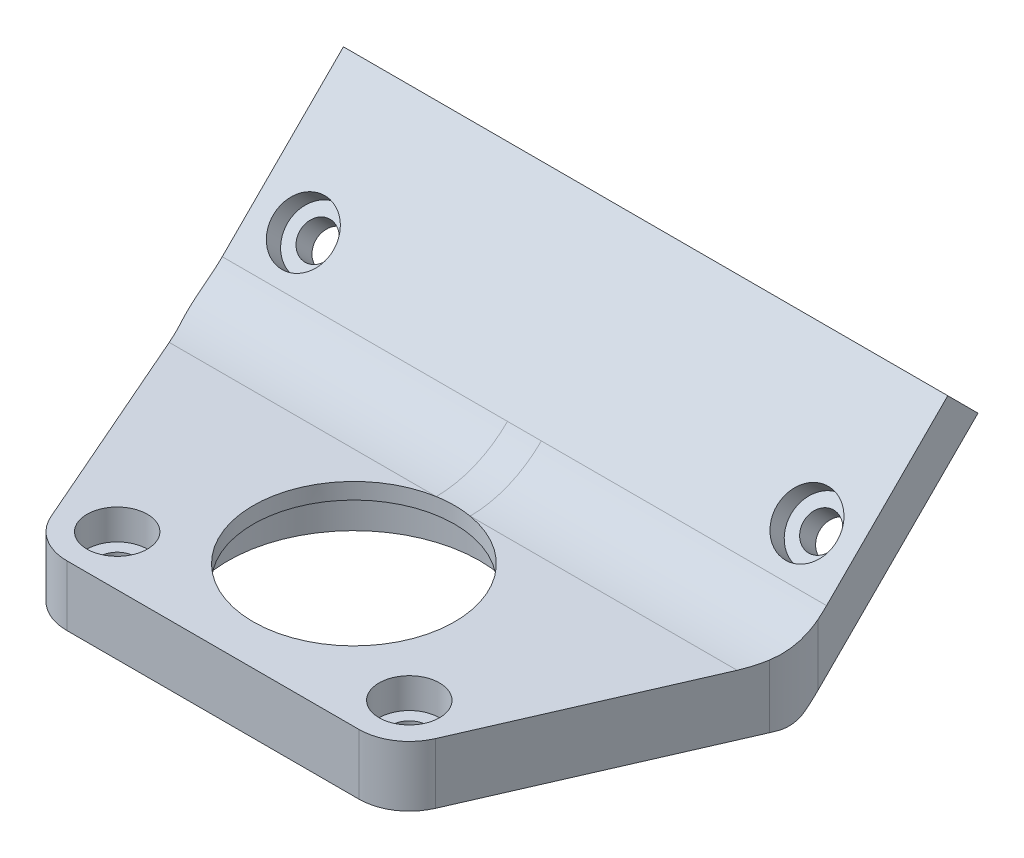
SolidWorks part; units mm, degrees
ref_plane "Alzado" through (0, 0, 0) normal (0, 0, 1) x (1, 0, 0)
ref_plane "Planta" through (0, 0, 0) normal (0, 1, 0) x (1, 0, 0)
ref_plane "Vista lateral" through (0, 0, 0) normal (1, 0, 0) x (0, 0, -1)
sketch "Croquis2" plane through (0, 0, 0) normal (1, 0, 0) x (0, 0, -1)
  line L0 (0, 0) -> (-28, 0)
  line L1 (-28, 0) -> (-28, 6)
  line L2 (-28, 6) -> (0, 6)
  line L3 (0, 6) -> (14.9605, 20.9605)
  line L4 (14.9605, 20.9605) -> (17.9605, 17.9605)
  line L5 (17.9605, 17.9605) -> (0, 0)
  dimension "D1" = 6
  dimension "D2" = 28
  dimension "D3" = 28
  dimension "D4" = 25.4
  dimension "D5" = 45
extrude "Saliente-Extruir1" add sketch "Croquis2" along normal blind 30 and the other way blind 30
ref_plane "Plano1" through (0, 0, 0) normal (0, -0.7071, -0.7071) x (-1, 0, 0)
sketch "Croquis3" plane through (0, 0, 0) normal (0, -0.7071, -0.7071) x (-1, 0, 0)
  line L0 (0, 0) -> (0, 25.4) construction
  line L1 (30, 25.4) -> (-30, 25.4) construction
  line L2 (-25, 12.7) -> (25, 12.7) construction
  circle A0 centre (-25, 12.7) radius 1.75
  circle A1 centre (25, 12.7) radius 1.75
  point P8 (0, 12.7)
  dimension "D2" = 3.5
  dimension "D1" = 50
extrude "Cortar-Extruir1" cut sketch "Croquis3" against normal up to surface (4.2426 mm away) up to face at (0, 13.4803, -7.4803)
ref_plane "Plano2" through (0, 3, 3) normal (0, 0.7071, 0.7071) x (1, 0, 0)
sketch "Croquis4" plane through (0, 3, 3) normal (0, 0.7071, 0.7071) x (1, 0, 0)
  circle A0 centre (-25, 12.7) radius 3
  circle A1 centre (25, 12.7) radius 3
  dimension "D1" = 6
extrude "Cortar-Extruir2" cut sketch "Croquis4" against normal blind 2
ref_plane "Plano3" through (0, 0, 0) normal (0, -1, 0) x (-1, 0, 0)
sketch "Croquis5" plane through (0, 0, 0) normal (0, -1, 0) x (-1, 0, 0)
  line L0 (14.5, -23) -> (-14.5, -23) construction
  line L1 (-30, 0) -> (-19.0821, -25.001)
  line L4 (-30, 0) -> (-30, -28)
  line L5 (-30, -28) -> (-14.5, -28)
  line L8 (0, 0) -> (0, -28) construction
  line L12 (30, -28) -> (-30, -28) construction
  line L13 (30, 0) -> (19.0821, -25.001)
  line L14 (30, 0) -> (30, -28)
  line L15 (30, -28) -> (14.5, -28)
  line L16 (0, -14) -> (0, -23) construction
  circle A0 centre (0, -14) radius 12.5
  circle A1 centre (0, -14) radius 12 construction
  circle A2 centre (0, -14) radius 10
  circle A3 centre (14.5, -23) radius 1.75
  circle A4 centre (-14.5, -23) radius 1.75
  arc A5 (-19.0821, -25.001) -> (-14.5, -28) centre (-14.5, -23) ccw
  arc A8 (19.0821, -25.001) -> (14.5, -28) centre (14.5, -23) cw
  circle A9 centre (-14.5, -23) radius 3 construction
  circle A10 centre (14.5, -23) radius 3 construction
  point P7 (0, -24)
  point P22 (0, -14)
  dimension "D1" = 24
  dimension "D2" = 20
  dimension "D3" = 25
  dimension "D4" = 3.5
  dimension "D7" = 6
  dimension "D5" = 29
  dimension "D6" = 9
extrude "Cortar-Extruir3" cut sketch "Croquis5" against normal up to surface (6 mm away) contours A2 | A3 | A4 | A5 L1 L4 L5 | L13 A8 L15 L14 region at (25.8314, 0, 18.7609) region at (-25.8314, 0, 18.7609) region at (0, 0, 14) region at (-14.5, 0, 23) region at (14.5, 0, 23) up to face at (0, 6, 14)
extrude "Cortar-Extruir4" cut sketch "Croquis5<4>" against normal blind 4.4 contours A0 A2 region at (12.1464, 0, 14)
sketch "Croquis5<4>" plane through (0, 0, 0) normal (0, -1, 0) x (-1, 0, 0) same geometry as "Croquis5"
fillet "Redondeo1" radius 10 1 edges at (0, 6, 0)
fillet "Redondeo2" radius 3 1 edges at (0, 0, 0)
fillet "Redondeo3" radius 10 2 edges at (-30, 3.5838, 0) (30, 3.5838, 0)
ref_plane "Plano4" through (0, 6, 0) normal (0, 1, 0) x (1, 0, 0)
sketch "Croquis6" plane through (0, 6, 0) normal (0, 1, 0) x (1, 0, 0)
  circle A0 centre (14.5, -23) radius 3
  circle A1 centre (-14.5, -23) radius 3
  dimension "D1" = 6
extrude "Cortar-Extruir5" cut sketch "Croquis6" against normal blind 3
